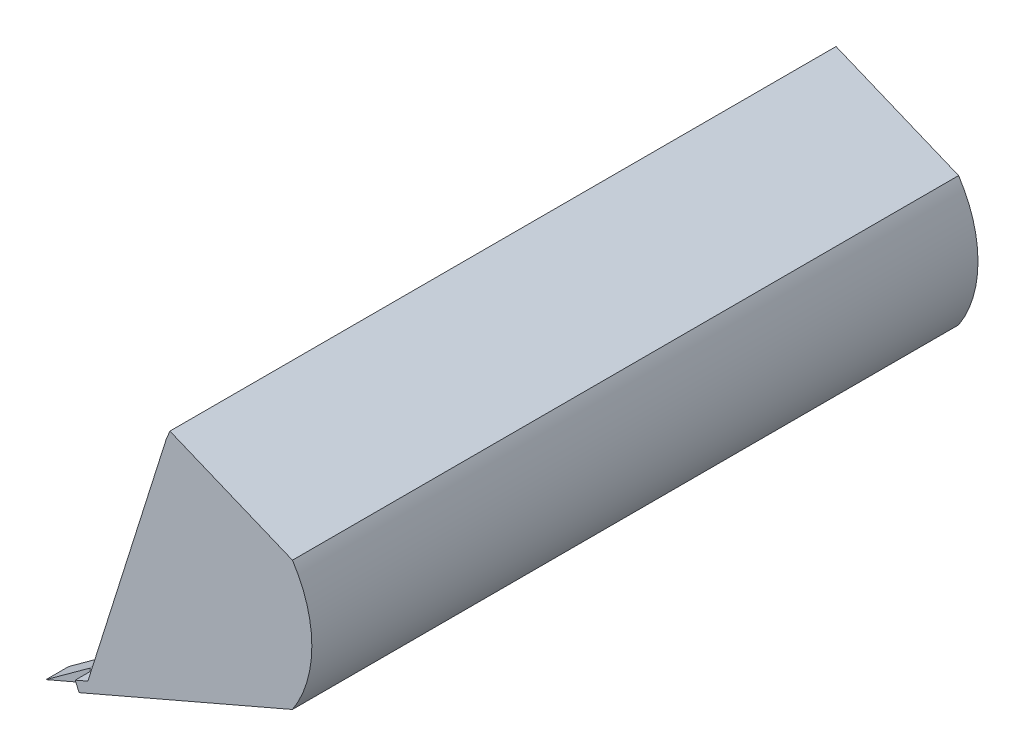
SolidWorks part; units mm, degrees
material "AISI 4340 Steel, normalized"
ref_plane "Front Plane" through (0, 0, 0) normal (0, 0, 1) x (1, 0, 0)
ref_plane "Top Plane" through (0, 0, 0) normal (0, 1, 0) x (1, 0, 0)
ref_plane "Right Plane" through (0, 0, 0) normal (1, 0, 0) x (0, 0, -1)
sketch "Sketch1" plane through (0, 0, 0) normal (0, 0, 1) x (1, 0, 0)
  line L0 (0, 0) -> (0, -400) construction
  line L1 (0, 0) -> (-379.065, 156.2362)
  line L2 (0, -400) -> (-660, -684.846)
  arc A0 (0, 0) -> (0, -400) centre (-303.3333, -200) cw
  point P3 (60, -200)
  point P4 (0, 0)
  dimension "D1" = 400
  dimension "D2" = 60
  dimension "D3" = 410
  dimension "D4" = 660
extrude "Extrude-Thin1" add sketch "Sketch1" along normal blind 2060.5751 thin thin type one direction wall 30
sketch "Sketch3" plane through (133.6396, -309.6484, 0) normal (-0.3963, 0.9181, 0) x (0.9181, 0.3963, 0)
  line L0 (-877.3466, -40) -> (-877.3466, -110)
  line L1 (-877.3466, -2060.5751) -> (-877.3466, 0) construction
  line L2 (-877.3466, -110) -> (-1057.3466, -110)
  line L3 (-877.3466, -40) -> (-1057.3466, -40)
  line L4 (-1057.3466, -40) -> (-1057.3466, -110)
  point P10 (-877.3466, -75)
  point P11 (-1122.8874, -65)
  point P12 (-1122.8874, -297.6242)
  point P14 (-1034.3166, -72)
  dimension "D1" = 70
  dimension "D2" = 180
  dimension "D3" = 180
  dimension "D5" = 40
extrude "Boss-Extrude2" add sketch "Sketch3" against normal blind 36
fillet "Fillet4" radius 20 2 edges at (-665.9438, -671.0739, 110) (-665.9438, -671.0739, 40)
fillet "Fillet6" radius 10 3 edges at (-669.1814, -688.8086, 110) (-660, -684.846, 75) (-669.1814, -688.8086, 40)
sketch "Sketch4" plane through (0, 0, 2060.5751) normal (0, 0, 1) x (1, 0, 0)
  line L0 (0, 0) -> (-379.065, 156.2362)
  line L1 (-379.065, 156.2362) -> (-390.4969, 128.4998)
  line L2 (-390.4969, 128.4998) -> (-644.7565, -678.2672)
  line L3 (0, -400) -> (-660, -684.846) construction
  line L4 (-644.7565, -678.2672) -> (0, -400)
  arc A0 (0, 0) -> (0, -400) centre (-308.3137, -200) cw
  point P3 (-644.7565, -678.2672)
extrude "Boss-Extrude3" add sketch "Sketch4" against normal blind 20
sketch "Sketch5" plane through (0, 0, 0) normal (0, 0, -1) x (-1, 0, 0)
  line L0 (0, 0) -> (379.065, 156.2362)
  line L1 (379.065, 156.2362) -> (390.4969, 128.4998)
  line L2 (390.4969, 128.4998) -> (644.6211, -678.2087)
  line L3 (0, -400) -> (660, -684.846) construction
  line L4 (644.6211, -678.2087) -> (0, -400)
  arc A0 (0, 0) -> (0, -400) centre (305.7683, -200) ccw
  point P3 (644.6211, -678.2087)
extrude "Boss-Extrude4" add sketch "Sketch5" against normal blind 20
pattern_linear "LPattern1" count 10 spacing 210 along (0, 0, 1) of "Fillet4", "Fillet6", "Boss-Extrude2"
sketch "Sketch7" plane through (0, 0, 110) normal (0, 0, 1) x (1, 0, 0)
  line L0 (-690.2505, -665.2269) -> (-822.8877, -761.6809)
  line L1 (-822.8877, -761.6809) -> (-837.1529, -728.6278)
  line L2 (-837.1529, -728.6278) -> (-690.2505, -665.2269)
extrude "Cut-Extrude2" cut sketch "Sketch7" against normal blind 94 and the other way blind 2004
